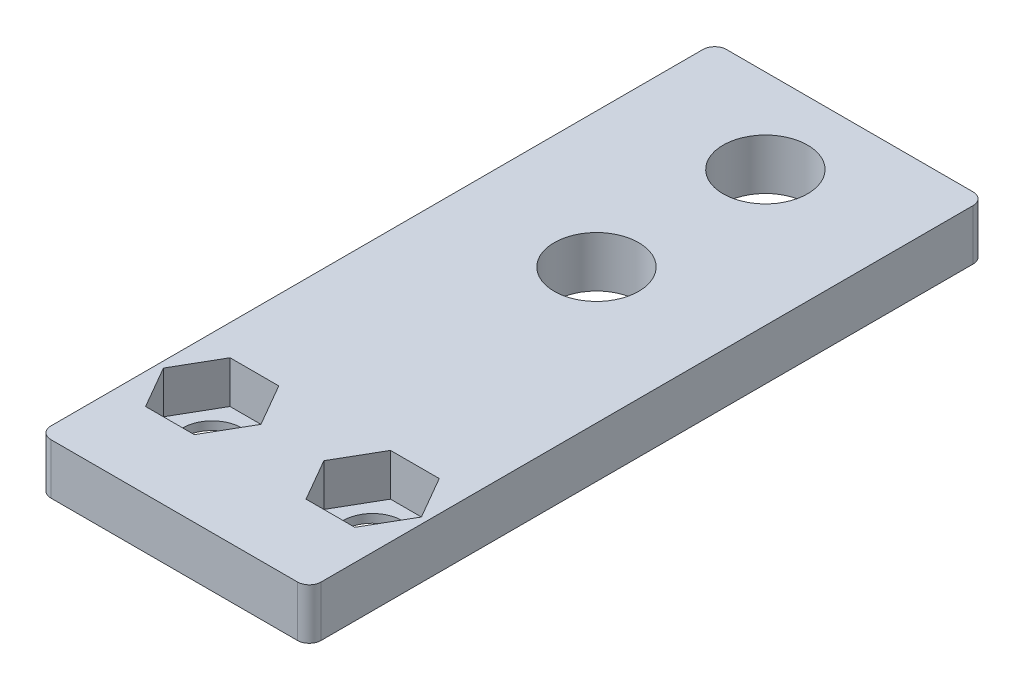
SolidWorks part; units mm, degrees
ref_plane "Front Plane" through (0, 0, 0) normal (0, 0, 1) x (1, 0, 0)
ref_plane "Top Plane" through (0, 0, 0) normal (0, 1, 0) x (1, 0, 0)
ref_plane "Right Plane" through (0, 0, 0) normal (1, 0, 0) x (0, 0, -1)
sketch "Sketch1" plane through (0, 0, 0) normal (0, 1, 0) x (1, 0, 0)
  line L0 (3.25, 7) -> (12.75, 7) construction
  line L1 (0, 0) -> (16, 0)
  line L2 (0, 0) -> (0, 40)
  line L3 (0, 40) -> (16, 40)
  line L4 (16, 0) -> (16, 40)
  line L5 (4.6934, 9.5) -> (1.8066, 9.5)
  line L6 (1.8066, 9.5) -> (0.3632, 7)
  line L7 (0.3632, 7) -> (1.8066, 4.5)
  line L8 (1.8066, 4.5) -> (4.6934, 4.5)
  line L9 (4.6934, 4.5) -> (6.1368, 7)
  line L10 (6.1368, 7) -> (4.6934, 9.5)
  line L11 (11.3066, 9.5) -> (9.8632, 7)
  line L12 (9.8632, 7) -> (11.3066, 4.5)
  line L13 (11.3066, 4.5) -> (14.1934, 4.5)
  line L14 (14.1934, 4.5) -> (15.6368, 7)
  line L15 (15.6368, 7) -> (14.1934, 9.5)
  line L16 (14.1934, 9.5) -> (11.3066, 9.5)
  circle A0 centre (8, 35) radius 2.5
  circle A1 centre (8, 25) radius 2.5
  circle A2 centre (3.25, 7) radius 1.75
  circle A3 centre (12.75, 7) radius 1.75
  circle A4 centre (3.25, 7) radius 2.5 construction
  circle A5 centre (12.75, 7) radius 2.5 construction
  point P13 (8, 7)
  point P28 (8, 0)
  point P29 (3.25, 4.5)
  point P30 (8, 40)
  dimension "D3" = 5
  dimension "D8" = 3.5
  dimension "D9" = 3.5
  dimension "D1" = 16
  dimension "D2" = 40
  dimension "D4" = 5
  dimension "D5" = 10
  dimension "D6" = 9.5
  dimension "D7" = 5
  dimension "D10" = 7
extrude "Boss-Extrude1" add sketch "Sketch1" along normal blind 3 contours L1 L4 L3 L2 A1 A0 L16 L15 L14 L13 L12 L11 L10 L9 L8 L7 L6 L5 region at (8, 0, -20.3054)
extrude "Boss-Extrude2" add sketch "Sketch1<3>" along normal blind 0.5 contours L9 L10 L5 L6 L7 L8 A2 | L15 L16 L11 L12 L13 L14 A3 region at (5.3489, 0, -8.2118) region at (12.75, 0, -9.4236)
sketch "Sketch1<3>" plane through (0, 0, 0) normal (0, 1, 0) x (1, 0, 0) same geometry as "Sketch1"
fillet "Fillet1" radius 0.7 4 edges at (0, 1.5, 0) (16, 1.5, 0) (16, 1.5, -40) (0, 1.5, -40)
